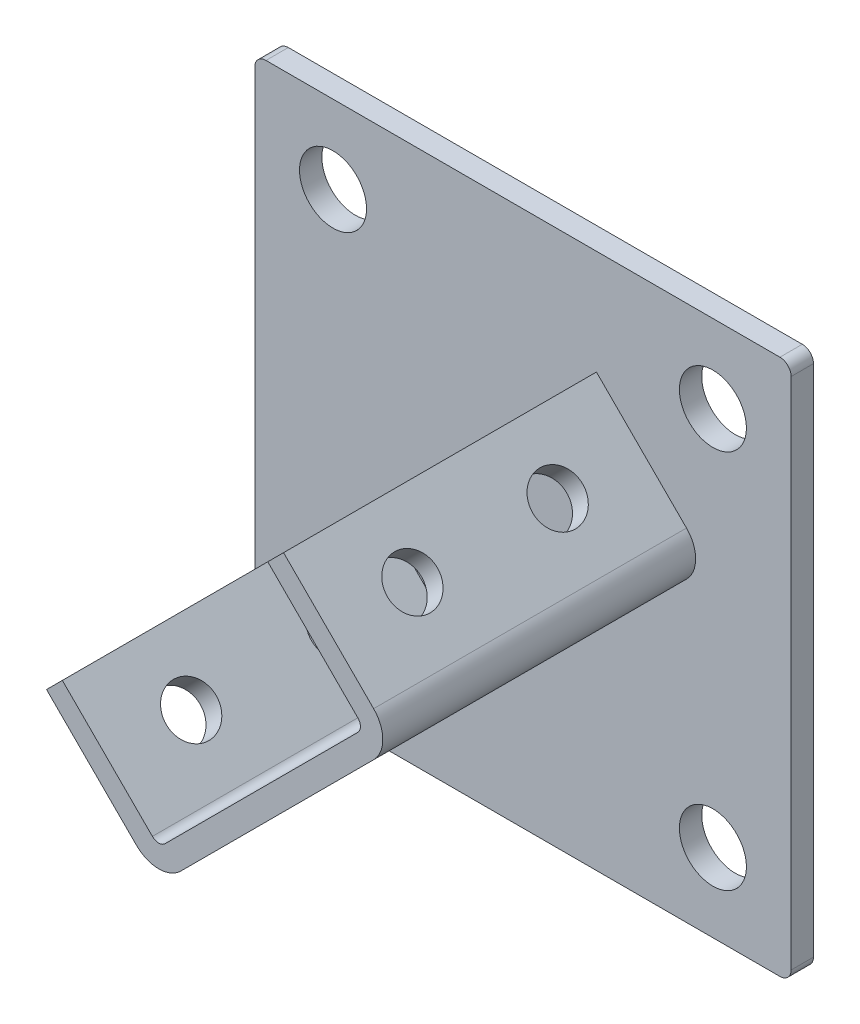
SolidWorks part; units mm, degrees
ref_plane "Front Plane" through (0, 0, 0) normal (0, 0, 1) x (1, 0, 0)
ref_plane "Top Plane" through (0, 0, 0) normal (0, 1, 0) x (1, 0, 0)
ref_plane "Right Plane" through (0, 0, 0) normal (1, 0, 0) x (0, 0, -1)
sketch "Sketch1" plane through (0, 0, 0) normal (0, 0, 1) x (1, 0, 0)
  line L0 (-76.2, -76.2) -> (76.2, 76.2) construction
  line L1 (-73.025, 76.2) -> (73.025, 76.2)
  line L2 (-76.2, 73.025) -> (-76.2, -73.025)
  line L3 (-73.025, -76.2) -> (73.025, -76.2)
  line L4 (76.2, 73.025) -> (76.2, -73.025)
  line L5 (-53.975, 53.975) -> (-53.975, -53.975) construction
  line L6 (-53.975, -53.975) -> (53.975, -53.975) construction
  line L7 (53.975, -53.975) -> (53.975, 53.975) construction
  line L8 (53.975, 53.975) -> (-53.975, 53.975) construction
  line L9 (-53.975, 53.975) -> (53.975, -53.975) construction
  circle A0 centre (-53.975, 53.975) radius 9.525
  circle A1 centre (-53.975, -53.975) radius 9.525
  arc A2 (76.2, 73.025) -> (73.025, 76.2) centre (73.025, 73.025) ccw
  arc A3 (-76.2, -73.025) -> (-73.025, -76.2) centre (-73.025, -73.025) ccw
  arc A4 (73.025, -76.2) -> (76.2, -73.025) centre (73.025, -73.025) ccw
  arc A5 (-73.025, 76.2) -> (-76.2, 73.025) centre (-73.025, 73.025) ccw
  circle A6 centre (53.975, 53.975) radius 9.525
  circle A7 centre (53.975, -53.975) radius 9.525
  point P19 (-76.2, 76.2)
  dimension "D3" = 19.05
  dimension "D6" = 3.175
  dimension "D1" = 152.4
  dimension "D2" = 152.4
  dimension "D4" = 107.95
extrude "Boss-Extrude1" add sketch "Sketch1" along normal blind 6.35
sketch "Sketch2" plane through (0, 0, 6.35) normal (0, 0, 1) x (1, 0, 0)
  line L0 (-58.3717, 0) -> (58.3717, 0) construction
  line L1 (-41.9827, -16.389) -> (-16.389, -41.9827)
  line L2 (-41.9827, -12.7969) -> (12.7969, 41.9827) construction
  line L3 (-12.7969, -41.9827) -> (41.9827, 12.7969)
  line L4 (16.389, 41.9827) -> (41.9827, 16.389)
  line L6 (40.1866, 14.5929) -> (-40.1866, -14.5929) construction
  line L7 (0, 0) -> (-29.1858, -29.1858) construction
  arc A0 (41.9827, 12.7969) -> (41.9827, 16.389) centre (40.1866, 14.5929) ccw
  arc A1 (12.7969, 41.9827) -> (16.389, 41.9827) centre (14.5929, 40.1866) cw construction
  arc A2 (-41.9827, -12.7969) -> (-41.9827, -16.389) centre (-40.1866, -14.5929) ccw construction
  arc A3 (-16.389, -41.9827) -> (-12.7969, -41.9827) centre (-14.5929, -40.1866) ccw
  dimension "D2" = 41.275
  dimension "D3" = 82.55
  dimension "D1" = 2.54
  dimension "D4" = 45
extrude "Extrude-Thin1" add sketch "Sketch2" along normal blind 88.9 thin thin type one direction wall 6.35
sketch "Sketch4" plane through (0, 0, 0) normal (1, 0, 0) x (0, 0, -1)
  line L0 (0, 0) -> (-45.4657, 0) construction
ref_plane "Plane1" through (0, 0, 0) normal (0.7071, -0.7071, 0) x (0, 0, 1)
sketch "Sketch3" plane through (0, 0, 0) normal (0.7071, -0.7071, 0) x (-0.7071, -0.7071, 0)
  line L0 (-38.735, -95.25) -> (-38.735, -6.35) construction
  line L1 (0, 0) -> (0, -45.4657) construction
  line L2 (0, -6.35) -> (0, -45.4657) construction
  line L3 (-20.6375, -30.1625) -> (-20.6375, -71.4375) construction
  line L4 (-20.6375, -50.8) -> (-38.735, -50.8) construction
  line L6 (-38.735, -6.35) -> (38.735, -6.35) construction
  circle A0 centre (-20.6375, -30.1625) radius 7.112
  circle A1 centre (-20.6375, -71.4375) radius 7.112
  circle A2 centre (20.6375, -71.4375) radius 7.112
  circle A3 centre (20.6375, -30.1625) radius 7.112
  dimension "D3" = 14.224
  dimension "D1" = 41.275
  dimension "D2" = 20.6375
extrude "Cut-Extrude1" cut sketch "Sketch3" along normal through all
ref_axis "Axis1" through (14.5929, 14.5929, 71.4375) along (0, 0, -1)
pattern_circular "CirPattern1" count 4 over 360 about axis through (14.5929, 14.5929, 71.4375) along (0, 0, -1) skipping 2 of "Cut-Extrude1"
